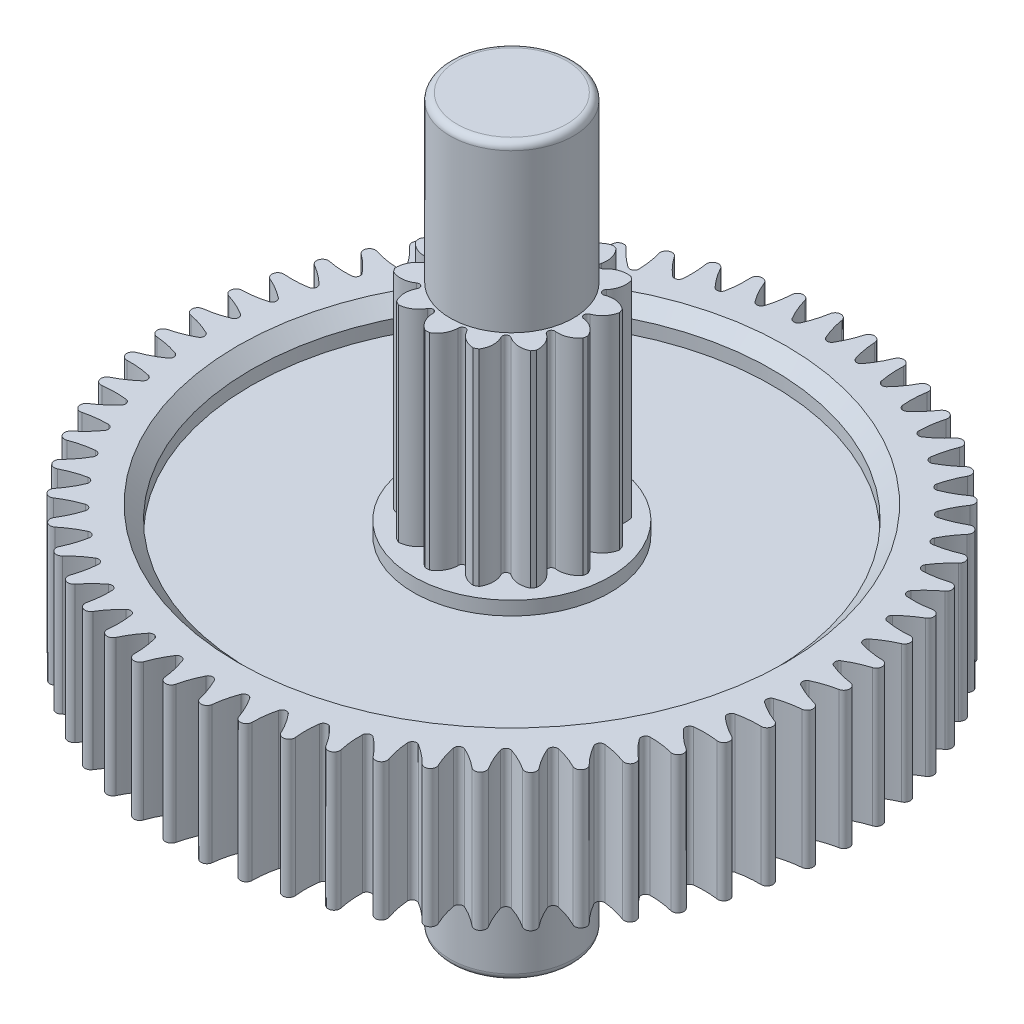
SolidWorks part; units mm, degrees
ref_plane "Front Plane" through (0, 0, 0) normal (0, 0, 1) x (1, 0, 0)
ref_plane "Top Plane" through (0, 0, 0) normal (0, 1, 0) x (1, 0, 0)
ref_plane "Right Plane" through (0, 0, 0) normal (1, 0, 0) x (0, 0, -1)
sketch "Sketch1" plane through (0, 0, 0) normal (0, 0, 1) x (1, 0, 0)
  line L0 (0, 0) -> (0, 53)
  line L1 (0, 53) -> (-4.5, 53)
  line L2 (-4.5, 53) -> (-4.5, 41)
  line L3 (-4.5, 41) -> (-6.175, 41)
  line L4 (-6.175, 41) -> (-6.175, 26)
  line L5 (-6.175, 26) -> (-7.175, 26)
  line L6 (-7.175, 26) -> (-7.175, 25)
  line L7 (-7.175, 25) -> (-19, 25)
  line L8 (-19, 25) -> (-19, 26)
  line L9 (-19, 26) -> (-20, 27)
  line L10 (-20, 27) -> (-24, 27)
  line L11 (-24, 27) -> (-24, 17)
  line L12 (-24, 17) -> (-20, 17)
  line L13 (-20, 17) -> (-19, 18)
  line L14 (-19, 18) -> (-19, 19)
  line L15 (-19, 19) -> (-8.5, 19)
  line L16 (-4.5, 15) -> (-4.5, 0)
  line L17 (-4.5, 0) -> (0, 0)
  line L18 (0, 53) -> (0, 0) construction
  arc A0 (-8.5, 19) -> (-4.5, 15) centre (-8.5, 15) cw
  dimension "D1" = 4
  dimension "D2" = 4.5
  dimension "D3" = 6.175
  dimension "D4" = 15
  dimension "D5" = 12
  dimension "D6" = 1
  dimension "D7" = 2
  dimension "D8" = 5
  dimension "D9" = 4
  dimension "D10" = 10
  dimension "D11" = 6
  dimension "D12" = 1
  dimension "D13" = 19
  dimension "D14" = 1
  dimension "D15" = 15
  dimension "D16" = 11.825
  dimension "D17" = 4.5
revolve "Revolve2" add sketch "Sketch1" angle 360 about L18
fillet "Fillet1" radius 0.5 2 edges at (-4.5, 0, 0) (-4.5, 53, 0)
sketch "Sketch3" plane through (0, 27, 0) normal (0, 1, 0) x (1, 0, 0)
  line L0 (0, 0) -> (0, 24) construction
  circle A0 centre (0, 0) radius 24 construction
  arc A1 (-0.4244, 23.6391) -> (0.4244, 23.6391) centre (0, 23.57) cw
  circle A2 centre (0, 0) radius 22 construction
  arc A3 (-0.4244, 23.6391) -> (-0.92, 21.9808) centre (-7.0669, 24.7209) cw
  arc A4 (0.4244, 23.6391) -> (0.92, 21.9808) centre (7.0669, 24.7209) ccw
  circle A5 centre (0, 0) radius 24
  arc A6 (3.0223, 23.449) -> (3.3325, 21.7461) centre (9.7435, 23.7935) ccw
  arc A7 (2.1787, 23.5423) -> (1.5036, 21.9486) centre (-4.3045, 25.3483) cw
  arc A8 (2.1787, 23.5423) -> (3.0223, 23.449) centre (2.5929, 23.4269) cw
  arc A9 (5.5836, 22.9742) -> (5.7045, 21.2476) centre (12.3018, 22.5772) ccw
  arc A10 (4.7553, 23.1598) -> (3.909, 21.6499) centre (-1.4898, 25.668) cw
  arc A11 (4.7553, 23.1598) -> (5.5836, 22.9742) centre (5.1543, 22.9995) cw
  arc A12 (8.077, 22.2205) -> (8.0073, 20.4911) centre (14.7109, 21.0869) ccw
  arc A13 (7.2742, 22.4961) -> (6.267, 21.0885) centre (1.3429, 25.6761) cw
  arc A14 (7.2742, 22.4961) -> (8.077, 22.2205) centre (7.6532, 22.2929) cw
  arc A15 (10.4724, 21.1971) -> (10.2129, 19.4858) centre (16.9413, 19.3406) ccw
  arc A16 (9.7048, 21.5593) -> (8.5489, 20.2711) centre (4.1593, 25.3725) cw
  arc A17 (9.7048, 21.5593) -> (10.4724, 21.1971) centre (10.0591, 21.3157) cw
  arc A18 (12.7407, 19.9164) -> (12.2945, 18.2441) centre (18.9661, 17.3595) ccw
  arc A19 (12.0176, 20.3609) -> (10.727, 19.2076) centre (6.9253, 24.761) cw
  arc A20 (12.0176, 20.3609) -> (12.7407, 19.9164) centre (12.343, 20.0797) cw
  arc A21 (14.8544, 18.3939) -> (14.2269, 16.7808) centre (20.7607, 15.1677) ccw
  arc A22 (14.1845, 18.9153) -> (12.7749, 17.911) centre (9.6072, 23.8489) cw
  arc A23 (14.1845, 18.9153) -> (14.8544, 18.3939) centre (14.477, 18.6) cw
  arc A24 (16.7877, 16.6482) -> (15.9866, 15.1139) centre (22.3033, 12.7918) ccw
  arc A25 (16.1793, 17.24) -> (14.6677, 16.3969) centre (12.1724, 22.6473) cw
  arc A26 (16.1793, 17.24) -> (16.7877, 16.6482) centre (16.4353, 16.8946) cw
  arc A27 (18.5172, 14.7003) -> (17.5522, 13.2635) centre (23.5751, 10.2606) ccw
  arc A28 (17.9776, 15.3556) -> (16.3824, 14.6839) centre (14.5899, 21.1707) cw
  arc A29 (17.9776, 15.3556) -> (18.5172, 14.7003) centre (18.1941, 14.984) cw
  arc A30 (20.022, 12.5741) -> (18.9047, 11.2521) centre (24.5608, 7.6049) ccw
  arc A31 (19.5578, 13.2847) -> (17.8984, 12.7925) centre (16.8303, 19.4372) cw
  arc A32 (19.5578, 13.2847) -> (20.022, 12.5741) centre (19.732, 12.8916) cw
  arc A33 (21.2837, 10.2952) -> (20.0278, 9.1042) centre (25.2483, 4.8569) ccw
  arc A34 (20.9005, 11.0525) -> (19.197, 10.7459) centre (18.8664, 17.4678) cw
  arc A35 (20.9005, 11.0525) -> (21.2837, 10.2952) centre (21.0304, 10.6426) cw
  arc A36 (22.2871, 7.8913) -> (20.9078, 6.8457) centre (25.6294, 2.0499) ccw
  arc A37 (21.9895, 8.6862) -> (20.2626, 8.5689) centre (20.6735, 15.2863) cw
  arc A38 (21.9895, 8.6862) -> (22.2871, 7.8913) centre (22.0736, 8.2645) cw
  arc A39 (23.02, 5.3916) -> (21.534, 4.5041) centre (25.6993, -0.782) ccw
  arc A40 (22.8116, 6.2145) -> (21.0823, 6.2878) centre (22.2297, 12.9193) cw
  arc A41 (22.8116, 6.2145) -> (23.02, 5.3916) centre (22.8488, 5.7861) cw
  arc A42 (23.4734, 2.8265) -> (21.8988, 2.1079) centre (25.4573, -3.6044) ccw
  arc A43 (23.3568, 3.6673) -> (21.6461, 3.9304) centre (23.516, 10.3954) cw
  arc A44 (23.3568, 3.6673) -> (23.4734, 2.8265) centre (23.3466, 3.2374) cw
  arc A45 (23.6418, 0.2271) -> (21.9978, -0.314) centre (24.9063, -6.383) ccw
  arc A46 (23.6185, 1.0756) -> (21.9471, 1.5253) centre (24.5168, 7.7454) cw
  arc A47 (23.6185, 1.0756) -> (23.6418, 0.2271) centre (23.5611, 0.6495) cw
  arc A48 (23.5233, -2.3751) -> (21.8297, -2.732) centre (24.0529, -9.0842) ccw
  arc A49 (23.5934, -1.5291) -> (21.9817, -0.8983) centre (25.2201, 5.0013) cw
  arc A50 (23.5934, -1.5291) -> (23.5233, -2.3751) centre (23.4895, -1.9464) cw
  arc A51 (23.1193, -4.9484) -> (21.3967, -5.1169) centre (22.9076, -11.6751) ccw
  arc A52 (23.282, -4.1153) -> (21.7494, -3.311) centre (25.6172, 2.1965) cw
  arc A53 (23.282, -4.1153) -> (23.1193, -4.9484) centre (23.1328, -4.5186) cw
  arc A54 (22.4346, -7.4617) -> (20.7039, -7.4396) centre (21.4842, -14.1242) ccw
  arc A55 (22.688, -6.6516) -> (21.2532, -5.6835) centre (25.7034, -0.6349) cw
  arc A56 (22.688, -6.6516) -> (22.4346, -7.4617) centre (22.4953, -7.036) cw
  arc A57 (21.4776, -9.8844) -> (19.7598, -9.6721) centre (19.8, -16.402) ccw
  arc A58 (21.8186, -9.1071) -> (20.4989, -7.9871) centre (25.4775, -3.4586) cw
  arc A59 (21.8186, -9.1071) -> (21.4776, -9.8844) centre (21.5848, -9.468) cw
  arc A60 (20.2599, -12.1871) -> (18.5759, -11.7871) centre (17.8755, -18.4806) ccw
  arc A61 (20.6843, -11.452) -> (19.4959, -10.1936) centre (24.9424, -6.2404) cw
  arc A62 (20.6843, -11.452) -> (20.2599, -12.1871) centre (20.4122, -11.785) cw
  arc A63 (18.7962, -14.3419) -> (17.1665, -13.7591) centre (15.734, -20.3349) ccw
  arc A64 (19.2989, -13.6579) -> (18.2562, -12.2765) centre (24.1045, -8.9464) cw
  arc A65 (19.2989, -13.6579) -> (18.7962, -14.3419) centre (18.9919, -13.959) cw
  arc A66 (17.1044, -16.3226) -> (15.5487, -15.564) centre (13.4015, -21.9423) ccw
  arc A67 (17.6793, -15.6981) -> (16.7949, -14.2103) centre (22.9741, -11.5438) cw
  arc A68 (17.6793, -15.6981) -> (17.1044, -16.3226) centre (17.341, -15.9635) cw
  arc A69 (15.205, -18.1051) -> (13.7421, -17.18) centre (10.9063, -23.2834) ccw
  arc A70 (15.8451, -17.5477) -> (15.1297, -15.9716) centre (21.5647, -14.001) cw
  arc A71 (15.8451, -17.5477) -> (15.205, -18.1051) centre (15.4796, -17.7743) cw
  arc A72 (13.121, -19.6679) -> (11.7688, -18.5875) centre (8.2788, -24.3419) ccw
  arc A73 (13.8185, -19.1843) -> (13.2808, -17.5391) centre (19.8936, -16.2884) cw
  arc A74 (13.8185, -19.1843) -> (13.121, -19.6679) centre (13.4304, -19.3693) cw
  arc A75 (10.8777, -20.992) -> (9.6526, -19.7694) centre (5.5507, -25.1049) ccw
  arc A76 (11.6242, -20.588) -> (11.2708, -18.8936) centre (17.981, -18.378) cw
  arc A77 (11.6242, -20.588) -> (10.8777, -20.992) centre (11.2181, -20.7292) cw
  arc A78 (8.5024, -22.0612) -> (7.4192, -20.7112) centre (2.7553, -25.5631) ccw
  arc A79 (9.2888, -21.7418) -> (9.1239, -20.0188) centre (15.8502, -20.2445) cw
  arc A80 (9.2888, -21.7418) -> (8.5024, -22.0612) centre (8.8696, -21.8375) cw
  arc A81 (6.0239, -22.8627) -> (5.0958, -21.4017) centre (-0.0736, -25.7111) ccw
  arc A82 (6.8407, -22.6317) -> (6.8663, -20.901) centre (13.5269, -21.8653) cw
  arc A83 (6.8407, -22.6317) -> (6.0239, -22.8627) centre (6.4135, -22.6807) cw
  arc A84 (3.4723, -23.3866) -> (2.7105, -21.8324) centre (-2.9016, -25.547) ccw
  arc A85 (4.3095, -23.2469) -> (4.5254, -21.5295) centre (11.0394, -23.2206) cw
  arc A86 (4.3095, -23.2469) -> (3.4723, -23.3866) centre (3.8795, -23.2485) cw
  arc A87 (0.8785, -23.6266) -> (0.2923, -21.9981) centre (-5.6943, -25.0727) ccw
  arc A88 (1.726, -23.5798) -> (2.1295, -21.8967) centre (8.418, -24.2941) cw
  arc A89 (1.726, -23.5798) -> (0.8785, -23.6266) centre (1.2984, -23.5342) cw
  arc A90 (-1.726, -23.5798) -> (-2.1295, -21.8967) centre (-8.418, -24.2941) ccw
  arc A91 (-0.8785, -23.6266) -> (-0.2923, -21.9981) centre (5.6943, -25.0727) cw
  arc A92 (-0.8785, -23.6266) -> (-1.726, -23.5798) centre (-1.2984, -23.5342) cw
  arc A93 (-4.3095, -23.2469) -> (-4.5254, -21.5295) centre (-11.0394, -23.2206) ccw
  arc A94 (-3.4723, -23.3866) -> (-2.7105, -21.8324) centre (2.9016, -25.547) cw
  arc A95 (-3.4723, -23.3866) -> (-4.3095, -23.2469) centre (-3.8795, -23.2485) cw
  arc A96 (-6.8407, -22.6317) -> (-6.8663, -20.901) centre (-13.5269, -21.8653) ccw
  arc A97 (-6.0239, -22.8627) -> (-5.0958, -21.4017) centre (0.0736, -25.7111) cw
  arc A98 (-6.0239, -22.8627) -> (-6.8407, -22.6317) centre (-6.4135, -22.6807) cw
  arc A99 (-9.2888, -21.7418) -> (-9.1239, -20.0188) centre (-15.8502, -20.2445) ccw
  arc A100 (-8.5024, -22.0612) -> (-7.4192, -20.7112) centre (-2.7553, -25.5631) cw
  arc A101 (-8.5024, -22.0612) -> (-9.2888, -21.7418) centre (-8.8696, -21.8375) cw
  arc A102 (-11.6242, -20.588) -> (-11.2708, -18.8936) centre (-17.981, -18.378) ccw
  arc A103 (-10.8777, -20.992) -> (-9.6526, -19.7694) centre (-5.5507, -25.1049) cw
  arc A104 (-10.8777, -20.992) -> (-11.6242, -20.588) centre (-11.2181, -20.7292) cw
  arc A105 (-13.8185, -19.1843) -> (-13.2808, -17.5391) centre (-19.8936, -16.2884) ccw
  arc A106 (-13.121, -19.6679) -> (-11.7688, -18.5875) centre (-8.2788, -24.3419) cw
  arc A107 (-13.121, -19.6679) -> (-13.8185, -19.1843) centre (-13.4304, -19.3693) cw
  arc A108 (-15.8451, -17.5477) -> (-15.1297, -15.9716) centre (-21.5647, -14.001) ccw
  arc A109 (-15.205, -18.1051) -> (-13.7421, -17.18) centre (-10.9063, -23.2834) cw
  arc A110 (-15.205, -18.1051) -> (-15.8451, -17.5477) centre (-15.4796, -17.7743) cw
  arc A111 (-17.6793, -15.6981) -> (-16.7949, -14.2103) centre (-22.9741, -11.5438) ccw
  arc A112 (-17.1044, -16.3226) -> (-15.5487, -15.564) centre (-13.4015, -21.9423) cw
  arc A113 (-17.1044, -16.3226) -> (-17.6793, -15.6981) centre (-17.341, -15.9635) cw
  arc A114 (-19.2989, -13.6579) -> (-18.2562, -12.2765) centre (-24.1045, -8.9464) ccw
  arc A115 (-18.7962, -14.3419) -> (-17.1665, -13.7591) centre (-15.734, -20.3349) cw
  arc A116 (-18.7962, -14.3419) -> (-19.2989, -13.6579) centre (-18.9919, -13.959) cw
  arc A117 (-20.6843, -11.452) -> (-19.4959, -10.1936) centre (-24.9424, -6.2404) ccw
  arc A118 (-20.2599, -12.1871) -> (-18.5759, -11.7871) centre (-17.8755, -18.4806) cw
  arc A119 (-20.2599, -12.1871) -> (-20.6843, -11.452) centre (-20.4122, -11.785) cw
  arc A120 (-21.8186, -9.1071) -> (-20.4989, -7.9871) centre (-25.4775, -3.4586) ccw
  arc A121 (-21.4776, -9.8844) -> (-19.7598, -9.6721) centre (-19.8, -16.402) cw
  arc A122 (-21.4776, -9.8844) -> (-21.8186, -9.1071) centre (-21.5848, -9.468) cw
  arc A123 (-22.688, -6.6516) -> (-21.2532, -5.6835) centre (-25.7034, -0.6349) ccw
  arc A124 (-22.4346, -7.4617) -> (-20.7039, -7.4396) centre (-21.4842, -14.1242) cw
  arc A125 (-22.4346, -7.4617) -> (-22.688, -6.6516) centre (-22.4953, -7.036) cw
  arc A126 (-23.282, -4.1153) -> (-21.7494, -3.311) centre (-25.6172, 2.1965) ccw
  arc A127 (-23.1193, -4.9484) -> (-21.3967, -5.1169) centre (-22.9076, -11.6751) cw
  arc A128 (-23.1193, -4.9484) -> (-23.282, -4.1153) centre (-23.1328, -4.5186) cw
  arc A129 (-23.5934, -1.5291) -> (-21.9817, -0.8983) centre (-25.2201, 5.0013) ccw
  arc A130 (-23.5233, -2.3751) -> (-21.8297, -2.732) centre (-24.0529, -9.0842) cw
  arc A131 (-23.5233, -2.3751) -> (-23.5934, -1.5291) centre (-23.4895, -1.9464) cw
  arc A132 (-23.6185, 1.0756) -> (-21.9471, 1.5253) centre (-24.5168, 7.7454) ccw
  arc A133 (-23.6418, 0.2271) -> (-21.9978, -0.314) centre (-24.9063, -6.383) cw
  arc A134 (-23.6418, 0.2271) -> (-23.6185, 1.0756) centre (-23.5611, 0.6495) cw
  arc A135 (-23.3568, 3.6673) -> (-21.6461, 3.9304) centre (-23.516, 10.3954) ccw
  arc A136 (-23.4734, 2.8265) -> (-21.8988, 2.1079) centre (-25.4573, -3.6044) cw
  arc A137 (-23.4734, 2.8265) -> (-23.3568, 3.6673) centre (-23.3466, 3.2374) cw
  arc A138 (-22.8116, 6.2145) -> (-21.0823, 6.2878) centre (-22.2297, 12.9193) ccw
  arc A139 (-23.02, 5.3916) -> (-21.534, 4.5041) centre (-25.6993, -0.782) cw
  arc A140 (-23.02, 5.3916) -> (-22.8116, 6.2145) centre (-22.8488, 5.7861) cw
  arc A141 (-21.9895, 8.6862) -> (-20.2626, 8.5689) centre (-20.6735, 15.2863) ccw
  arc A142 (-22.2871, 7.8913) -> (-20.9078, 6.8457) centre (-25.6294, 2.0499) cw
  arc A143 (-22.2871, 7.8913) -> (-21.9895, 8.6862) centre (-22.0736, 8.2645) cw
  arc A144 (-20.9005, 11.0525) -> (-19.197, 10.7459) centre (-18.8664, 17.4678) ccw
  arc A145 (-21.2837, 10.2952) -> (-20.0278, 9.1042) centre (-25.2483, 4.8569) cw
  arc A146 (-21.2837, 10.2952) -> (-20.9005, 11.0525) centre (-21.0304, 10.6426) cw
  arc A147 (-19.5578, 13.2847) -> (-17.8984, 12.7925) centre (-16.8303, 19.4372) ccw
  arc A148 (-20.022, 12.5741) -> (-18.9047, 11.2521) centre (-24.5608, 7.6049) cw
  arc A149 (-20.022, 12.5741) -> (-19.5578, 13.2847) centre (-19.732, 12.8916) cw
  arc A150 (-17.9776, 15.3556) -> (-16.3824, 14.6839) centre (-14.5899, 21.1707) ccw
  arc A151 (-18.5172, 14.7003) -> (-17.5522, 13.2635) centre (-23.5751, 10.2606) cw
  arc A152 (-18.5172, 14.7003) -> (-17.9776, 15.3556) centre (-18.1941, 14.984) cw
  arc A153 (-16.1793, 17.24) -> (-14.6677, 16.3969) centre (-12.1724, 22.6473) ccw
  arc A154 (-16.7877, 16.6482) -> (-15.9866, 15.1139) centre (-22.3033, 12.7918) cw
  arc A155 (-16.7877, 16.6482) -> (-16.1793, 17.24) centre (-16.4353, 16.8946) cw
  arc A156 (-14.1845, 18.9153) -> (-12.7749, 17.911) centre (-9.6072, 23.8489) ccw
  arc A157 (-14.8544, 18.3939) -> (-14.2269, 16.7808) centre (-20.7607, 15.1677) cw
  arc A158 (-14.8544, 18.3939) -> (-14.1845, 18.9153) centre (-14.477, 18.6) cw
  arc A159 (-12.0176, 20.3609) -> (-10.727, 19.2076) centre (-6.9253, 24.761) ccw
  arc A160 (-12.7407, 19.9164) -> (-12.2945, 18.2441) centre (-18.9661, 17.3595) cw
  arc A161 (-12.7407, 19.9164) -> (-12.0176, 20.3609) centre (-12.343, 20.0797) cw
  arc A162 (-9.7048, 21.5593) -> (-8.5489, 20.2711) centre (-4.1593, 25.3725) ccw
  arc A163 (-10.4724, 21.1971) -> (-10.2129, 19.4858) centre (-16.9413, 19.3406) cw
  arc A164 (-10.4724, 21.1971) -> (-9.7048, 21.5593) centre (-10.0591, 21.3157) cw
  arc A165 (-7.2742, 22.4961) -> (-6.267, 21.0885) centre (-1.3429, 25.6761) ccw
  arc A166 (-8.077, 22.2205) -> (-8.0073, 20.4911) centre (-14.7109, 21.0869) cw
  arc A167 (-8.077, 22.2205) -> (-7.2742, 22.4961) centre (-7.6532, 22.2929) cw
  arc A168 (-4.7553, 23.1598) -> (-3.909, 21.6499) centre (1.4898, 25.668) ccw
  arc A169 (-5.5836, 22.9742) -> (-5.7045, 21.2476) centre (-12.3018, 22.5772) cw
  arc A170 (-5.5836, 22.9742) -> (-4.7553, 23.1598) centre (-5.1543, 22.9995) cw
  arc A171 (-2.1787, 23.5423) -> (-1.5036, 21.9486) centre (4.3045, 25.3483) ccw
  arc A172 (-3.0223, 23.449) -> (-3.3325, 21.7461) centre (-9.7435, 23.7935) cw
  arc A173 (-3.0223, 23.449) -> (-2.1787, 23.5423) centre (-2.5929, 23.4269) cw
  arc A174 (-1.5036, 21.9486) -> (-0.92, 21.9808) centre (-1.2201, 22.1145) ccw
  arc A175 (0.92, 21.9808) -> (1.5036, 21.9486) centre (1.2201, 22.1145) ccw
  arc A176 (3.3325, 21.7461) -> (3.909, 21.6499) centre (3.6455, 21.8461) ccw
  arc A177 (5.7045, 21.2476) -> (6.267, 21.0885) centre (6.0266, 21.3125) ccw
  arc A178 (8.0073, 20.4911) -> (8.5489, 20.2711) centre (8.3346, 20.5201) ccw
  arc A179 (10.2129, 19.4858) -> (10.727, 19.2076) centre (10.5414, 19.4787) ccw
  arc A180 (12.2945, 18.2441) -> (12.7749, 17.911) centre (12.6202, 18.2009) ccw
  arc A181 (14.2269, 16.7808) -> (14.6677, 16.3969) centre (14.5459, 16.7021) ccw
  arc A182 (15.9866, 15.1139) -> (16.3824, 14.6839) centre (16.2949, 15.0005) ccw
  arc A183 (17.5522, 13.2635) -> (17.8984, 12.7925) centre (17.8462, 13.1169) ccw
  arc A184 (18.9047, 11.2521) -> (19.197, 10.7459) centre (19.1809, 11.0741) ccw
  arc A185 (20.0278, 9.1042) -> (20.2626, 8.5689) centre (20.2827, 8.8968) ccw
  arc A186 (20.9078, 6.8457) -> (21.0823, 6.2878) centre (21.1383, 6.6116) ccw
  arc A187 (21.534, 4.5041) -> (21.6461, 3.9304) centre (21.7373, 4.246) ccw
  arc A188 (21.8988, 2.1079) -> (21.9471, 1.5253) centre (22.0725, 1.829) ccw
  arc A189 (21.9978, -0.314) -> (21.9817, -0.8983) centre (22.1398, -0.6103) ccw
  arc A190 (21.8297, -2.732) -> (21.7494, -3.311) centre (21.9382, -3.0421) ccw
  arc A191 (21.3967, -5.1169) -> (21.2532, -5.6835) centre (21.4704, -5.4371) ccw
  arc A192 (20.7039, -7.4396) -> (20.4989, -7.9871) centre (20.742, -7.766) ccw
  arc A193 (19.7598, -9.6721) -> (19.4959, -10.1936) centre (19.7618, -10.0006) ccw
  arc A194 (18.5759, -11.7871) -> (18.2562, -12.2765) centre (18.5417, -12.1139) ccw
  arc A195 (17.1665, -13.7591) -> (16.7949, -14.2103) centre (17.0965, -14.0801) ccw
  arc A196 (15.5487, -15.564) -> (15.1297, -15.9716) centre (15.4438, -15.8754) ccw
  arc A197 (13.7421, -17.18) -> (13.2808, -17.5391) centre (13.6037, -17.478) ccw
  arc A198 (11.7688, -18.5875) -> (11.2708, -18.8936) centre (11.5984, -18.8685) ccw
  arc A199 (9.6526, -19.7694) -> (9.1239, -20.0188) centre (9.4523, -20.0299) ccw
  arc A200 (7.4192, -20.7112) -> (6.8663, -20.901) centre (7.1915, -20.9481) ccw
  arc A201 (5.0958, -21.4017) -> (4.5254, -21.5295) centre (4.8434, -21.6121) ccw
  arc A202 (2.7105, -21.8324) -> (2.1295, -21.8967) centre (2.4365, -22.0137) ccw
  arc A203 (0.2923, -21.9981) -> (-0.2923, -21.9981) centre (0, -22.1482) ccw
  arc A204 (-2.1295, -21.8967) -> (-2.7105, -21.8324) centre (-2.4365, -22.0137) ccw
  arc A205 (-4.5254, -21.5295) -> (-5.0958, -21.4017) centre (-4.8434, -21.6121) ccw
  arc A206 (-6.8663, -20.901) -> (-7.4192, -20.7112) centre (-7.1915, -20.9481) ccw
  arc A207 (-9.1239, -20.0188) -> (-9.6526, -19.7694) centre (-9.4523, -20.0299) ccw
  arc A208 (-11.2708, -18.8936) -> (-11.7688, -18.5875) centre (-11.5984, -18.8685) ccw
  arc A209 (-13.2808, -17.5391) -> (-13.7421, -17.18) centre (-13.6037, -17.478) ccw
  arc A210 (-15.1297, -15.9716) -> (-15.5487, -15.564) centre (-15.4438, -15.8754) ccw
  arc A211 (-16.7949, -14.2103) -> (-17.1665, -13.7591) centre (-17.0965, -14.0801) ccw
  arc A212 (-18.2562, -12.2765) -> (-18.5759, -11.7871) centre (-18.5417, -12.1139) ccw
  arc A213 (-19.4959, -10.1936) -> (-19.7598, -9.6721) centre (-19.7618, -10.0006) ccw
  arc A214 (-20.4989, -7.9871) -> (-20.7039, -7.4396) centre (-20.742, -7.766) ccw
  arc A215 (-21.2532, -5.6835) -> (-21.3967, -5.1169) centre (-21.4704, -5.4371) ccw
  arc A216 (-21.7494, -3.311) -> (-21.8297, -2.732) centre (-21.9382, -3.0421) ccw
  arc A217 (-21.9817, -0.8983) -> (-21.9978, -0.314) centre (-22.1398, -0.6103) ccw
  arc A218 (-21.9471, 1.5253) -> (-21.8988, 2.1079) centre (-22.0725, 1.829) ccw
  arc A219 (-21.6461, 3.9304) -> (-21.534, 4.5041) centre (-21.7373, 4.246) ccw
  arc A220 (-21.0823, 6.2878) -> (-20.9078, 6.8457) centre (-21.1383, 6.6116) ccw
  arc A221 (-20.2626, 8.5689) -> (-20.0278, 9.1042) centre (-20.2827, 8.8968) ccw
  arc A222 (-19.197, 10.7459) -> (-18.9047, 11.2521) centre (-19.1809, 11.0741) ccw
  arc A223 (-17.8984, 12.7925) -> (-17.5522, 13.2635) centre (-17.8462, 13.1169) ccw
  arc A224 (-16.3824, 14.6839) -> (-15.9866, 15.1139) centre (-16.2949, 15.0005) ccw
  arc A225 (-14.6677, 16.3969) -> (-14.2269, 16.7808) centre (-14.5459, 16.7021) ccw
  arc A226 (-12.7749, 17.911) -> (-12.2945, 18.2441) centre (-12.6202, 18.2009) ccw
  arc A227 (-10.727, 19.2076) -> (-10.2129, 19.4858) centre (-10.5414, 19.4787) ccw
  arc A228 (-8.5489, 20.2711) -> (-8.0073, 20.4911) centre (-8.3346, 20.5201) ccw
  arc A229 (-6.267, 21.0885) -> (-5.7045, 21.2476) centre (-6.0266, 21.3125) ccw
  arc A230 (-3.909, 21.6499) -> (-3.3325, 21.7461) centre (-3.6455, 21.8461) ccw
  point P410 (0, 0)
  point P579 (0, 0)
  circle M3 centre (0, 0) radius 24
  dimension "D1" = 0.43
  dimension "D2" = 44
  dimension "D3" = 6.73
  dimension "D4" = 6.73
  dimension "D5" = 1.84
  dimension "D6" = 57
  dimension "D7" = 57
extrude "Cut-Extrude1" cut sketch "Sketch3" against normal blind 10 contours A4 A175 A7 A8 A5 A1 | A171 A174 A3 A1 A173 M3 | A6 A176 A10 A11 A5 A8 | A9 A177 A13 A14 A5 A11 | A12 A178 A16 A17 A5 A14 | A15 A179 A19 A20 A5 A17 | A18 A180 A22 A23 A5 A20 | A21 A181 A25 A26 A5 A23 | A24 A182 A28 A29 A5 A26 | A27 A183 A31 A32 A5 A29 | A30 A184 A34 A35 A5 A32 | A33 A185 A37 A38 A5 A35 | A36 A186 A40 A41 A5 A38 | A39 A187 A43 A44 A5 A41 | A42 A188 A46 A47 A5 A44 | A45 A189 A49 A50 A5 A47 | A48 A190 A52 A53 A5 A50 | A51 A191 A55 A56 A5 A53 | A54 A192 A58 A59 A5 A56 | A57 A193 A61 A62 A5 A59 | A60 A194 A64 A65 A5 A62 | A63 A195 A67 A68 A5 A65 | A66 A196 A70 A71 A5 A68 | A69 A197 A73 A74 A5 A71 | A72 A198 A76 A77 A5 A74 | A75 A199 A79 A80 A5 A77 | A78 A200 A82 A83 A5 A80 | A81 A201 A85 A86 A5 A83 | A84 A202 A88 A89 A5 A86 | A87 A203 A91 A92 A5 A89 | A90 A204 A94 A95 A5 A92 | A93 A205 A97 A98 A5 A95 | A96 A206 A100 A101 A5 A98 | A99 A207 A103 A104 A5 A101 | A102 A208 A106 A107 A5 A104 | A105 A209 A109 A110 A5 A107 | A108 A210 A112 A113 A5 A110 | A111 A211 A115 A116 A5 A113 | A114 A212 A118 A119 A5 A116 | A117 A213 A121 A122 A5 A119 | A120 A214 A124 A125 A5 A122 | A126 A216 A130 A131 A5 A128 | A129 A217 A133 A134 A5 A131 | A132 A218 A136 A137 A5 A134 | A123 A215 A127 A128 A5 A125 | A135 A219 A139 A140 A5 A137 | A138 A220 A142 A143 A5 A140 | A141 A221 A145 A146 A5 A143 | A144 A222 A148 A149 A5 A146 | A147 A223 A151 A152 A5 A149 | A150 A224 A154 A155 A5 A152 | A153 A225 A157 A158 A5 A155 | A156 A226 A160 A161 A5 A158 | A162 A228 A166 A167 A5 A164 | A165 A229 A169 A170 A5 A167 | A168 A230 A172 A173 A5 A170 | A159 A227 A163 A164 A5 A161 region at (-1.2746, 27, -23.1031) region at (1.2746, 27, -23.1031) region at (3.8084, 27, -22.8226) region at (-3.8084, 27, -22.8226) region at (6.296, 27, -22.2651) region at (-6.296, 27, -22.2651) region at (8.7071, 27, -21.4374) region at (-8.7071, 27, -21.4374) region at (11.0126, 27, -20.3494) region at (-11.0126, 27, -20.3494) region at (13.1843, 27, -19.0144) region at (-13.1843, 27, -19.0144) region at (15.1961, 27, -17.4487) region at (-15.1961, 27, -17.4487) region at (17.0233, 27, -15.6711) region at (-17.0233, 27, -15.6711) region at (18.6439, 27, -13.7032) region at (-18.6439, 27, -13.7032) region at (20.0383, 27, -11.5691) region at (-20.0383, 27, -11.5691) region at (21.1893, 27, -9.2945) region at (-21.1893, 27, -9.2945) region at (22.0832, 27, -6.9071) region at (-22.0832, 27, -6.9071) region at (22.709, 27, -4.4358) region at (-22.709, 27, -4.4358) region at (23.0592, 27, -1.9107) region at (-23.0592, 27, -1.9107) region at (23.1294, 27, 0.6376) region at (-23.1294, 27, 0.6376) region at (-22.9189, 27, 3.1781) region at (22.9189, 27, 3.1781) region at (-22.4302, 27, 5.6801) region at (22.4302, 27, 5.6801) region at (-21.6692, 27, 8.1131) region at (21.6692, 27, 8.1131) region at (-20.6451, 27, 10.4477) region at (20.6451, 27, 10.4477) region at (-19.3705, 27, 12.6554) region at (19.3705, 27, 12.6554) region at (-17.8608, 27, 14.7095) region at (17.8608, 27, 14.7095) region at (-16.1342, 27, 16.585) region at (16.1342, 27, 16.585) region at (-14.2118, 27, 18.2593) region at (14.2118, 27, 18.2593) region at (-12.1168, 27, 19.7119) region at (12.1168, 27, 19.7119) region at (-9.8748, 27, 20.9252) region at (9.8748, 27, 20.9252) region at (-7.513, 27, 21.8845) region at (7.513, 27, 21.8845) region at (-5.0599, 27, 22.5782) region at (5.0599, 27, 22.5782) region at (-2.5454, 27, 22.9978) region at (2.5454, 27, 22.9978) region at (0, 27, 23.1382)
sketch "Sketch4" plane through (0, 41, 0) normal (0, 1, 0) x (1, 0, 0)
  line L0 (0, 0) -> (0, 6.175) construction
  circle A0 centre (0, 0) radius 6.175 construction
  circle A1 centre (0, 0) radius 6.175
  circle A2 centre (0, 0) radius 4.925 construction
  arc A3 (-0.26, 4.9181) -> (-1.32, 6.0323) centre (-1.7734, 4.5396) ccw
  arc A4 (0.26, 4.9181) -> (1.32, 6.0323) centre (1.7734, 4.5396) cw
  arc A5 (2.0554, 4.4756) -> (1.6345, 5.9547) centre (0.5394, 4.8437) ccw
  arc A6 (2.5158, 4.234) -> (3.9721, 4.7279) centre (3.6799, 3.1955) cw
  arc A7 (3.8998, 3.0078) -> (4.2146, 4.5131) centre (2.7286, 4.0382) ccw
  arc A8 (4.1952, 2.5798) -> (5.7143, 2.3404) centre (4.7434, 1.1193) cw
  arc A9 (4.8509, 0.8509) -> (5.8292, 2.0375) centre (4.2927, 2.3076) ccw
  arc A10 (4.9136, 0.3347) -> (6.1474, -0.5833) centre (4.7203, -1.2133) cw
  arc A11 (4.6907, -1.5009) -> (6.1083, -0.9048) centre (4.8734, 0.0484) ccw
  arc A12 (4.5063, -1.9871) -> (5.1722, -3.3733) centre (3.6158, -3.2679) cw
  arc A13 (3.4559, -3.5089) -> (4.9882, -3.6399) centre (4.3377, -2.222) ccw
  arc A14 (3.0667, -3.8537) -> (3.0121, -5.3905) centre (1.6829, -4.5739) cw
  arc A15 (1.4294, -4.713) -> (2.7253, -5.5411) centre (2.8082, -3.9833) ccw
  arc A16 (0.9245, -4.8374) -> (0.162, -6.1729) centre (-0.6354, -4.8321) cw
  arc A17 (-0.9245, -4.8374) -> (-0.162, -6.1729) centre (0.6354, -4.8321) ccw
  arc A18 (-1.4294, -4.713) -> (-2.7253, -5.5411) centre (-2.8082, -3.9833) cw
  arc A19 (-3.0667, -3.8537) -> (-3.0121, -5.3905) centre (-1.6829, -4.5739) ccw
  arc A20 (-3.4559, -3.5089) -> (-4.9882, -3.6399) centre (-4.3377, -2.222) cw
  arc A21 (-4.5063, -1.9871) -> (-5.1722, -3.3733) centre (-3.6158, -3.2679) ccw
  arc A22 (-4.6907, -1.5009) -> (-6.1083, -0.9048) centre (-4.8734, 0.0484) cw
  arc A23 (-4.9136, 0.3347) -> (-6.1474, -0.5833) centre (-4.7203, -1.2133) ccw
  arc A24 (-4.8509, 0.8509) -> (-5.8292, 2.0375) centre (-4.2927, 2.3076) cw
  arc A25 (-4.1952, 2.5798) -> (-5.7143, 2.3404) centre (-4.7434, 1.1193) ccw
  arc A26 (-3.8998, 3.0078) -> (-4.2146, 4.5131) centre (-2.7286, 4.0382) cw
  arc A27 (-2.5158, 4.234) -> (-3.9721, 4.7279) centre (-3.6799, 3.1955) ccw
  arc A28 (-2.0554, 4.4756) -> (-1.6345, 5.9547) centre (-0.5394, 4.8437) cw
  arc A29 (4.5063, -1.9871) -> (4.6907, -1.5009) centre (4.6427, -1.7608) cw
  arc A30 (3.0667, -3.8537) -> (3.4559, -3.5089) centre (3.2927, -3.7167) cw
  arc A31 (0.9245, -4.8374) -> (1.4294, -4.713) centre (1.1883, -4.8211) cw
  arc A32 (-1.4294, -4.713) -> (-0.9245, -4.8374) centre (-1.1883, -4.8211) cw
  arc A33 (-3.4559, -3.5089) -> (-3.0667, -3.8537) centre (-3.2927, -3.7167) cw
  arc A34 (-4.6907, -1.5009) -> (-4.5063, -1.9871) centre (-4.6427, -1.7608) cw
  arc A35 (-4.8509, 0.8509) -> (-4.9136, 0.3347) centre (-4.9292, 0.5985) cw
  arc A36 (-3.8998, 3.0078) -> (-4.1952, 2.5798) centre (-4.0864, 2.8207) cw
  arc A37 (-2.0554, 4.4756) -> (-2.5158, 4.234) centre (-2.3075, 4.3966) cw
  arc A38 (0.26, 4.9181) -> (-0.26, 4.9181) centre (0, 4.9654) cw
  arc A39 (2.5158, 4.234) -> (2.0554, 4.4756) centre (2.3075, 4.3966) cw
  arc A40 (4.1952, 2.5798) -> (3.8998, 3.0078) centre (4.0864, 2.8207) cw
  arc A41 (4.9136, 0.3347) -> (4.8509, 0.8509) centre (4.9292, 0.5985) cw
  point P89 (0, 0)
  point P127 (0, 0)
  dimension "D1" = 9.85
  dimension "D4" = 1.56
  dimension "D5" = 1.56
  dimension "D9" = 0.2643
  dimension "D2" = 2.64
  dimension "D3" = 1.32
  dimension "D6" = 0.26
  dimension "D7" = 0.26
  dimension "D8" = 13
  dimension "D10" = 13
extrude "Cut-Extrude2" cut sketch "Sketch4" against normal blind 15 contours A37 A28 A1 A27 | A38 A4 A1 A3 | A39 A6 A1 A5 | A40 A8 A1 A7 | A41 A10 A1 A9 | A29 A12 A1 A11 | A30 A14 A1 A13 | A31 A16 A1 A15 | A32 A18 A1 A17 | A33 A20 A1 A19 | A34 A22 A1 A21 | A35 A24 A1 A23 | A36 A26 A1 A25 region at (5.6102, 41, -0.6812) region at (4.651, 41, -3.2104) region at (5.2842, 41, 2.004) region at (2.6263, 41, -5.0041) region at (3.7476, 41, 4.2302) region at (0, 41, -5.6514) region at (1.3525, 41, 5.4872) region at (-2.6263, 41, -5.0041) region at (-1.3525, 41, 5.4872) region at (-4.651, 41, -3.2104) region at (-3.7476, 41, 4.2302) region at (-5.6102, 41, -0.6812) region at (-5.2842, 41, 2.004)
